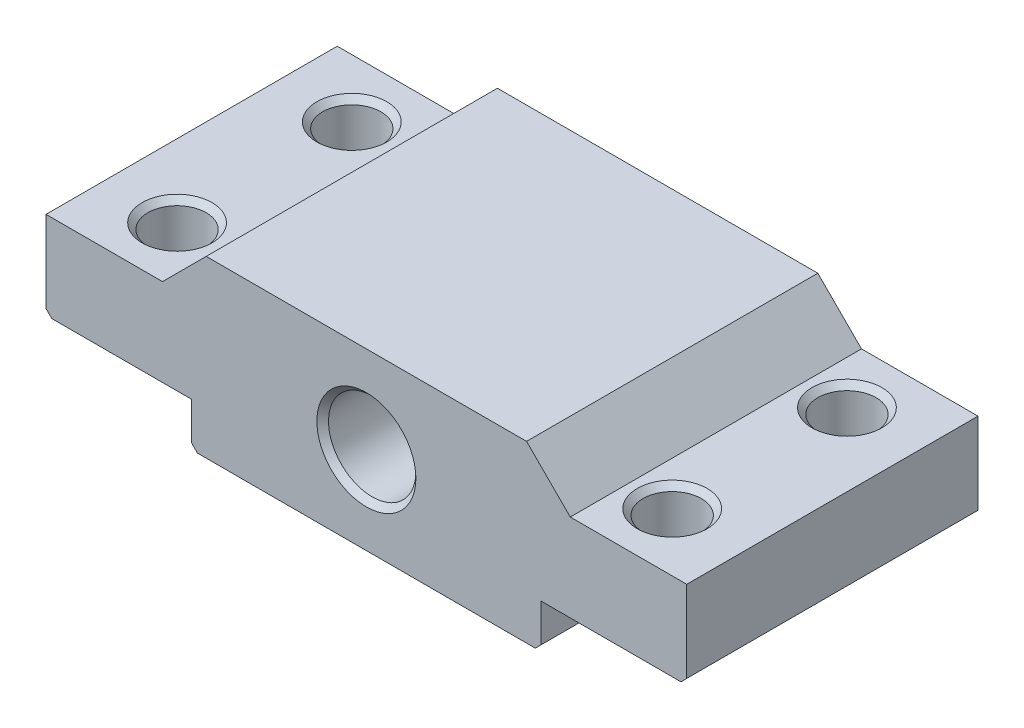
SolidWorks part; units mm, degrees
ref_plane "Front Plane" through (0, 0, 0) normal (0, 0, 1) x (1, 0, 0)
ref_plane "Top Plane" through (0, 0, 0) normal (0, 1, 0) x (1, 0, 0)
ref_plane "Right Plane" through (0, 0, 0) normal (1, 0, 0) x (0, 0, -1)
sketch "Sketch1" plane through (0, 0, 0) normal (0, 0, 1) x (1, 0, 0)
  line L0 (-55, -6.5) -> (-55, 7.5)
  line L1 (-55, 7.5) -> (-25, 7.5)
  line L2 (-25, 7.5) -> (-25, 15)
  line L3 (-25, 15) -> (25, 15)
  line L4 (25, 15) -> (25, 7.5)
  line L5 (25, 7.5) -> (55, 7.5)
  line L6 (55, 7.5) -> (55, -6.5)
  line L7 (54, -7.5) -> (30, -7.5)
  line L8 (30, -7.5) -> (30, -14)
  line L9 (29, -15) -> (-29, -15)
  line L10 (-30, -14) -> (-30, -7.5)
  line L11 (-30, -7.5) -> (-54, -7.5)
  line L12 (0, 0) -> (0, 67.0922) construction
  line L13 (0, 0) -> (69.7731, 0) construction
  line L14 (-29, -15) -> (-30, -14)
  line L15 (30, -14) -> (29, -15)
  line L16 (55, -6.5) -> (54, -7.5)
  line L17 (-54, -7.5) -> (-55, -6.5)
  point P0 (-55, -7.5)
  point P8 (55, -7.5)
  point P10 (30, -15)
  point P11 (-30, -15)
  point P15 (0, 0)
  point P16 (0, 0)
  dimension "D1" = 110
  dimension "D2" = 60
  dimension "D3" = 50
  dimension "D4" = 15
  dimension "D5" = 15
  dimension "D6" = 15
  dimension "D7" = 1
  dimension "D8" = 45
  dimension "D9" = 1
  dimension "D10" = 45
  dimension "D11" = 1
  dimension "D12" = 45
  dimension "D13" = 1
  dimension "D14" = 45
extrude "Boss-Extrude1" add sketch "Sketch1" along normal mid plane 50
chamfer "Chamfer2" distance 10 angle 45 2 edges at (25, 7.5, 0) (-25, 7.5, 0)
hole_wizard "Hole1" positions "Sketch2" profile "Sketch3" legacy end condition up to next
sketch "Sketch2" plane through (0, 0, 25) normal (0, 0, 1) x (1, 0, 0)
  point P0 (0, 0)
sketch "Sketch3" plane through (0, 0, 25) normal (1, 0, 0) x (0, -1, 0)
  line L0 (0, 0) -> (0, 50)
  line L1 (0, 50) -> (7.5, 50)
  line L2 (7.5, 50) -> (7.5, 0)
  line L3 (7.5, 0) -> (0, 0)
  line L4 (0, 110) -> (0, -10) construction
  dimension "Diameter" = 15
  dimension "Depth" = 50
chamfer "Chamfer3" distance 1 angle 45 2 edges at (7.5, 0, -25) (7.5, 0, 25)
hole_wizard "Hole2" positions "Sketch4" profile "Sketch5" legacy end condition up to next
sketch "Sketch4" plane through (0, 7.5, 0) normal (0, 1, 0) x (1, 0, 0)
  point P0 (42.5, 15)
  point P2 (42.5, -15)
  point P6 (0, 0)
  point P7 (42.5, -16.979)
  dimension "D1" = 30
  dimension "D2" = 42.5
  dimension "D3" = 15
sketch "Sketch5" plane through (42.5, 7.5, -15) normal (1, 0, 0) x (0, 0, 1)
  line L0 (0, 0) -> (0, 15)
  line L1 (0, 15) -> (5, 15)
  line L2 (5, 15) -> (5, 0)
  line L3 (5, 0) -> (0, 0)
  line L4 (0, 110) -> (0, -10) construction
  dimension "Diameter" = 10
  dimension "Depth" = 15
chamfer "Chamfer4" distance 1 angle 45 4 edges at (37.5, -7.5, -15) (37.5, -7.5, 15) (42.5, 7.5, 20) (42.5, 7.5, -10)
mirror "Mirror5" about plane through (0, 0, 0) normal (1, 0, 0) of "Hole2"
chamfer "Chamfer5" distance 1 angle 45 4 edges at (-42.5, 7.5, -10) (-47.5, -7.5, -15) (-47.5, -7.5, 15) (-42.5, 7.5, 20)
